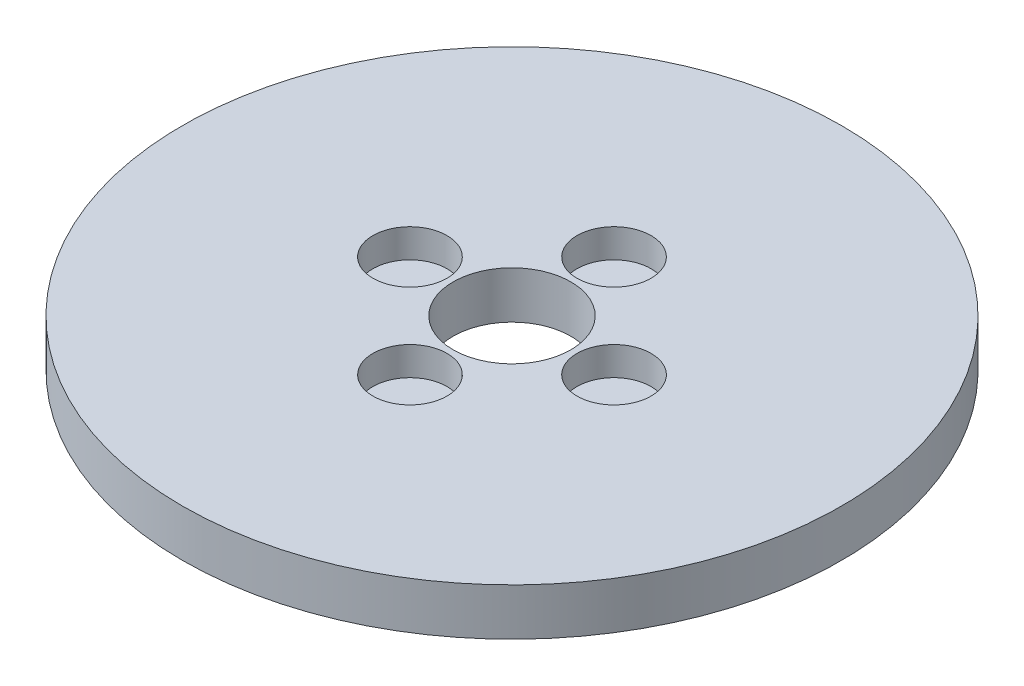
SolidWorks part; units mm, degrees
ref_plane "Front Plane" through (0, 0, 0) normal (0, 0, 1) x (1, 0, 0)
ref_plane "Top Plane" through (0, 0, 0) normal (0, 1, 0) x (1, 0, 0)
ref_plane "Right Plane" through (0, 0, 0) normal (1, 0, 0) x (0, 0, -1)
sketch "Sketch1" plane through (0, 0, 0) normal (0, 1, 0) x (1, 0, 0)
  circle A0 centre (0, 0) radius 70
  dimension "FLANGE_OD" = 140
extrude "Boss-Extrude1" add sketch "Sketch1" along normal blind 10
sketch "Sketch2" plane through (0, 0, 0) normal (0, 1, 0) x (1, 0, 0)
  circle A0 centre (0, 0) radius 12.5
  dimension "BORE_D" = 25
extrude "Cut-Extrude1" cut sketch "Sketch2" along normal through all
sketch "Sketch3" plane through (0, 10, 0) normal (0, 1, 0) x (1, 0, 0)
  circle A0 centre (0, 0) radius 21.6731 construction
  circle A1 centre (-21.6731, 0) radius 7.866
  dimension "BOLT_D" = 15.732
  dimension "BOLT_PCD" = 43.3461
extrude "Cut-Extrude2" cut sketch "Sketch3" against normal blind 6.1017
pattern_circular "CirPattern1" count 4 over 360 about axis through (0, 0, 0) along (0, 1, 0) of "Cut-Extrude2"
